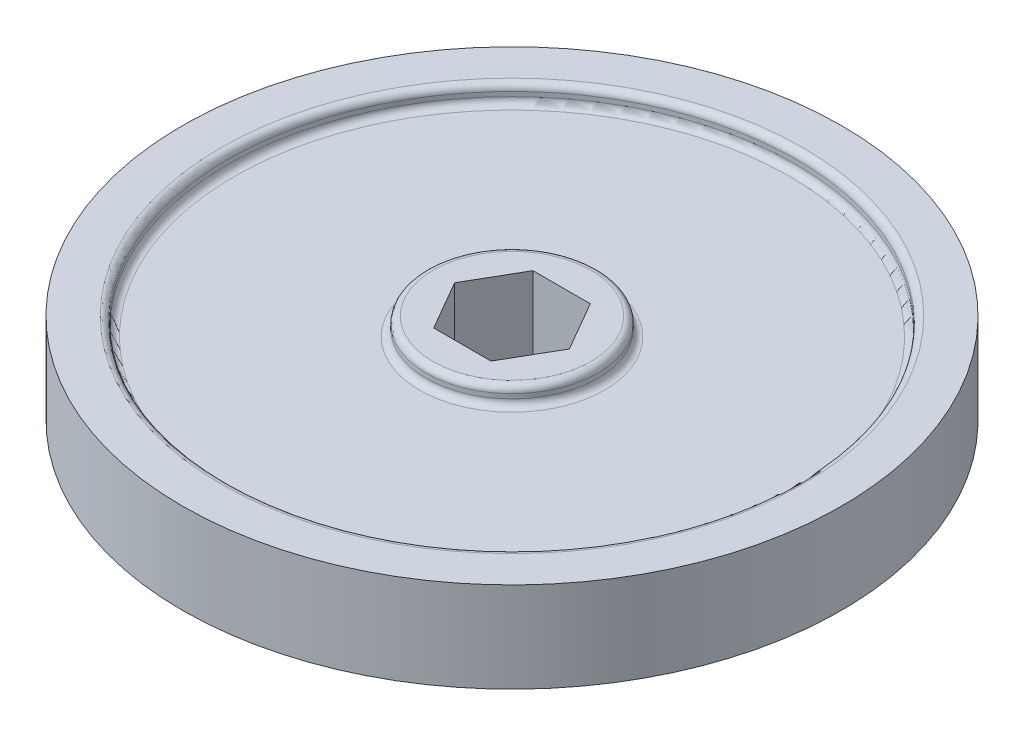
SolidWorks part; units mm, degrees
ref_plane "Piano frontale" through (0, 0, 0) normal (0, 0, 1) x (1, 0, 0)
ref_plane "Piano superiore" through (0, 0, 0) normal (0, 1, 0) x (1, 0, 0)
ref_plane "Piano destro" through (0, 0, 0) normal (1, 0, 0) x (0, 0, -1)
ref_plane "Piano1" through (0, 0, 0) normal (0, 0, -1) x (-1, 0, 0)
sketch "Schizzo1" plane through (0, 0, 0) normal (0, 0, -1) x (-1, 0, 0)
  line L0 (-36.5, -5) -> (0, -5)
  line L1 (0, -5) -> (0, 5)
  line L2 (0, 5) -> (-36.5, 5)
  line L3 (-36.5, 5) -> (-36.5, -5)
  line L4 (0, -5) -> (0, 5) construction
revolve "Rivoluzione1" add sketch "Schizzo1" angle 360 about L4 reverse direction yes
hole_wizard "Foro Ø6.3 (6.3)-1" positions "Schizzo3" profile "Schizzo2" hole size "Ø6.3" standard "Ansi Metric"
sketch "Schizzo3" plane through (0, -5, 0) normal (0, -1, 0) x (-1, 0, 0)
  point P0 (0, 0)
sketch "Schizzo2" plane through (0, -5, 0) normal (1, 0, 0) x (0, 0, -1)
  line L0 (0, 0) -> (0, 2)
  line L1 (0, 2) -> (31.5, 2)
  line L2 (31.5, 2) -> (31.5, 0)
  line L5 (31.5, 0) -> (0, 0)
  line L10 (0, 2) -> (-31.5, 2) construction
  line L11 (0, -6.35) -> (0, 107.95) construction
  dimension "Hole Dia." = 63
  dimension "Hole Depth" = 2
  dimension "Drill Angle" = 180
sketch "Schizzo4" plane through (0, -3, 0) normal (0, -1, 0) x (1, 0, 0)
  circle A0 centre (0, 0) radius 9.5
extrude "Estrusione-Estrusione1" add sketch "Schizzo4" along normal blind 2
hole_wizard "Foro Ø6.3 (6.3)-2" positions "Schizzo6" profile "Schizzo5" hole size "Ø6.3" standard "Ansi Metric"
sketch "Schizzo6" plane through (0, 5, 0) normal (0, 1, 0) x (1, 0, 0)
  point P0 (0, 0)
sketch "Schizzo5" plane through (0, 5, 0) normal (1, 0, 0) x (0, 0, 1)
  line L0 (0, 0) -> (0, 2)
  line L1 (0, 2) -> (31.5, 2)
  line L2 (31.5, 2) -> (31.5, 0)
  line L5 (31.5, 0) -> (0, 0)
  line L10 (0, 2) -> (-31.5, 2) construction
  line L11 (0, -6.35) -> (0, 107.95) construction
  dimension "Hole Dia." = 63
  dimension "Hole Depth" = 2
  dimension "Drill Angle" = 180
sketch "Schizzo7" plane through (0, 3, 0) normal (0, 1, 0) x (-1, 0, 0)
  circle A0 centre (0, 0) radius 9.5
extrude "Estrusione-Estrusione2" add sketch "Schizzo7" along normal blind 2
sketch "Schizzo8" plane through (0, 5, 0) normal (0, 1, 0) x (-1, 0, 0)
  line L0 (-3.175, -5.4993) -> (3.175, -5.4993)
  line L1 (3.175, -5.4993) -> (6.35, 0)
  line L2 (6.35, 0) -> (3.175, 5.4993)
  line L3 (3.175, 5.4993) -> (-3.175, 5.4993)
  line L4 (-3.175, 5.4993) -> (-6.35, 0)
  line L5 (-6.35, 0) -> (-3.175, -5.4993)
extrude "Taglio-Estrusione1" cut sketch "Schizzo8" against normal through all
fillet "Raccordo1" radius 0.75 8 edges at (0, 3, 31.5) (0, 3, -9.5) (0, 5, 31.5) (0, -3, 9.5) (0, 5, 9.5) (0, -5, -9.5) (0, -5, -31.5) (0, -3, -31.5) tangent propagation no
